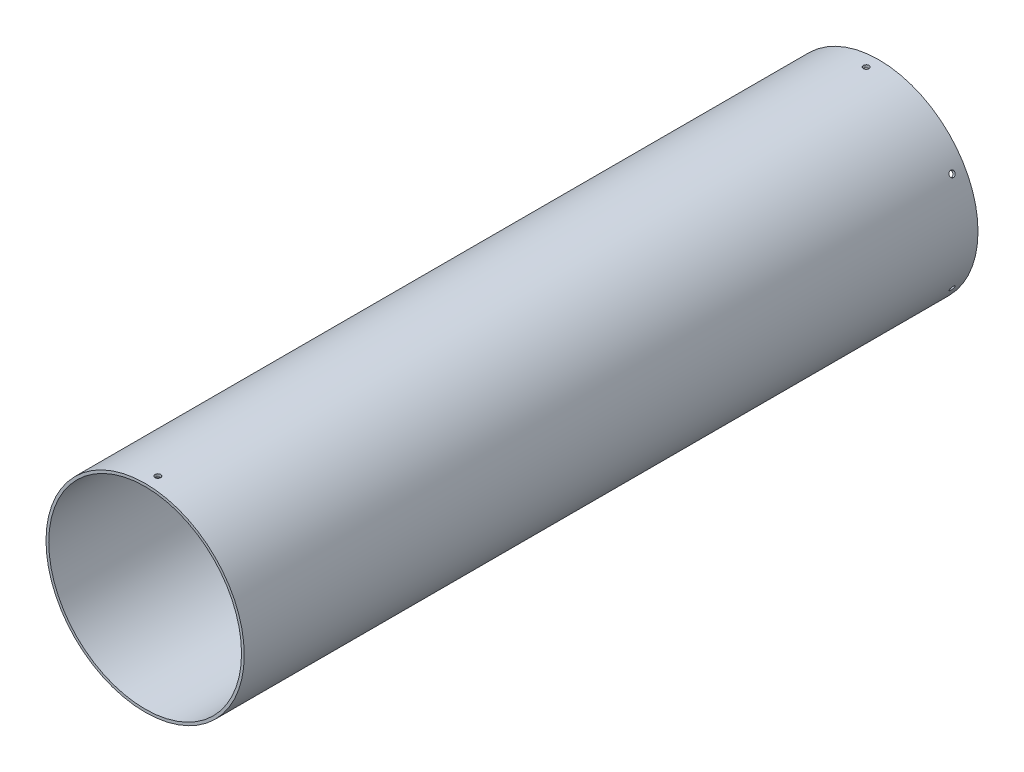
SolidWorks part; units mm, degrees
material "A-Glass Fiber"
ref_plane "Front Plane" through (0, 0, 0) normal (0, 0, 1) x (1, 0, 0)
ref_plane "Top Plane" through (0, 0, 0) normal (0, 1, 0) x (1, 0, 0)
ref_plane "Right Plane" through (0, 0, 0) normal (1, 0, 0) x (0, 0, -1)
sketch "Sketch1" plane through (0, 0, 0) normal (0, 0, 1) x (1, 0, 0)
  circle A0 centre (0, 0) radius 76.2
  circle A1 centre (0, 0) radius 78.359
  dimension "D1" = 156.718
  dimension "D2" = 152.4
extrude "Boss-Extrude1" add sketch "Sketch1" along normal blind 580
sketch "Sketch4" plane through (0, 0, 0) normal (0, 1, 0) x (1, 0, 0)
  line L0 (78.359, 0) -> (-78.359, 0) construction
  point P0 (0, -10)
  dimension "D1" = 10
hole_wizard "M4 Clearance Hole2" positions "Sketch4" profile "Sketch5" hole size "M4" standard "ANSI Metric" end condition through all
sketch "Sketch5" plane through (0, 0, 10) normal (1, 0, 0) x (0, 0, 1)
  line L0 (0, 0) -> (0, 78.359)
  line L1 (0, 78.359) -> (2.25, 78.359)
  line L2 (2.25, 78.359) -> (2.25, 0)
  line L5 (2.25, 0) -> (0, 0)
  line L11 (0, -6.35) -> (0, 107.95) construction
  dimension "Thru Hole Dia." = 4.5
  dimension "Thru Hole Depth" = 78.359
pattern_circular "CirPattern1" count 6 over 360 about axis through (0, 0, 580) along (0, 0, -1) of "M4 Clearance Hole2" reverse direction yes
sketch "Sketch6" plane through (0, 0, 0) normal (0, 1, 0) x (1, 0, 0)
  line L0 (-78.359, -580) -> (78.359, -580) construction
  point P0 (0, -570)
  dimension "D1" = 10
hole_wizard "M4 Clearance Hole3" positions "Sketch6" profile "Sketch7" hole size "M4" standard "ANSI Metric" end condition through all
sketch "Sketch7" plane through (0, 0, 570) normal (1, 0, 0) x (0, 0, -1)
  line L0 (0, 0) -> (0, 78.359)
  line L1 (0, 78.359) -> (2.25, 78.359)
  line L2 (2.25, 78.359) -> (2.25, 0)
  line L5 (2.25, 0) -> (0, 0)
  line L11 (0, -6.35) -> (0, 107.95) construction
  dimension "Thru Hole Dia." = 4.5
  dimension "Thru Hole Depth" = 78.359
